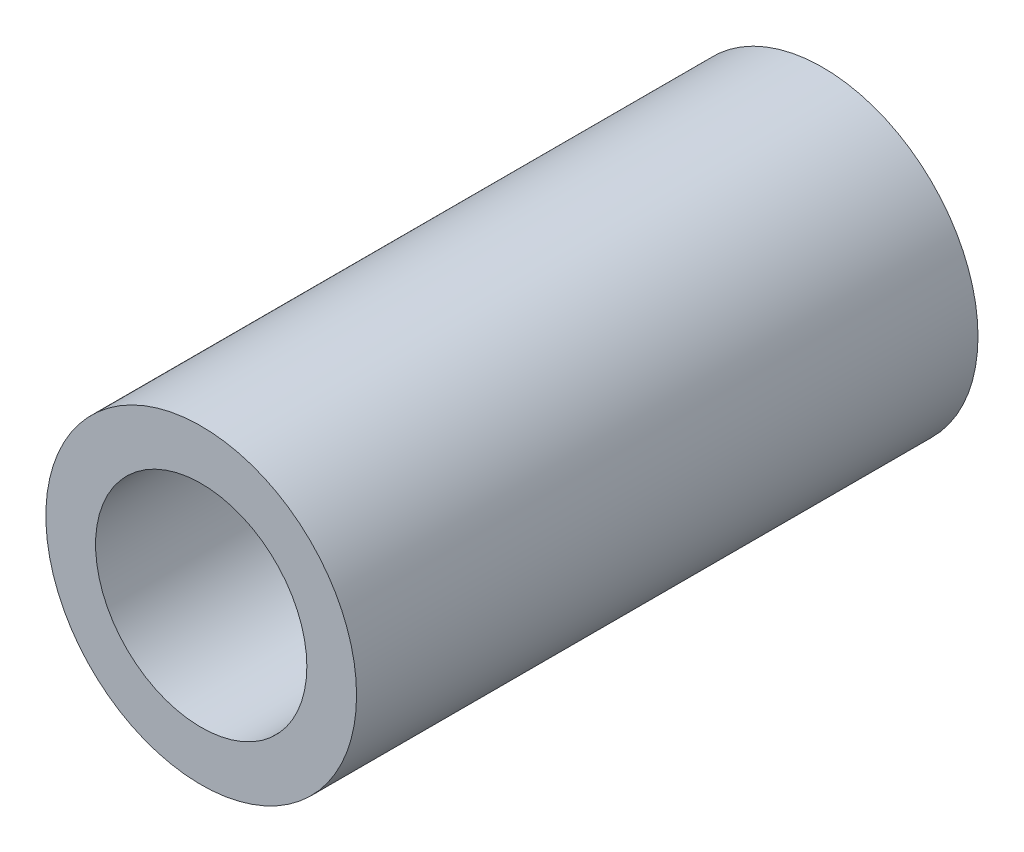
SolidWorks part; units mm, degrees
ref_plane "Front Plane" through (0, 0, 0) normal (0, 0, 1) x (1, 0, 0)
ref_plane "Top Plane" through (0, 0, 0) normal (0, 1, 0) x (1, 0, 0)
ref_plane "Right Plane" through (0, 0, 0) normal (1, 0, 0) x (0, 0, -1)
sketch "Sketch1" plane through (0, 0, 0) normal (0, 0, 1) x (1, 0, 0)
  circle A0 centre (0, 0) radius 12.5
  dimension "D1" = 25
extrude "Boss-Extrude1" add sketch "Sketch1" along normal blind 25 and the other way blind 25 contours A0
sketch "Sketch2" plane through (0, 0, 25) normal (0, 0, 1) x (1, 0, 0)
  circle A0 centre (0, 0) radius 8.5
  dimension "D1" = 17
extrude "Cut-Extrude1" cut sketch "Sketch2" against normal blind 50
